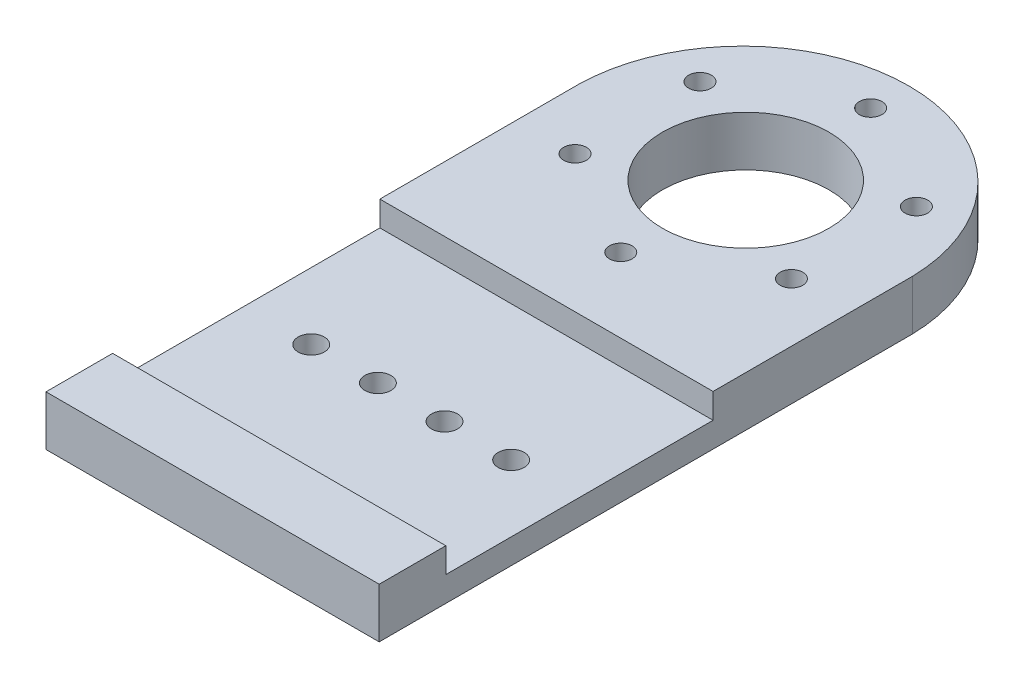
SolidWorks part; units mm, degrees
ref_plane "Front Plane" through (0, 0, 0) normal (0, 0, 1) x (1, 0, 0)
ref_plane "Top Plane" through (0, 0, 0) normal (0, 1, 0) x (1, 0, 0)
ref_plane "Right Plane" through (0, 0, 0) normal (1, 0, 0) x (0, 0, -1)
sketch "Sketch1" plane through (0, 0, 0) normal (0, 1, 0) x (1, 0, 0)
  line L0 (0, -111.3091) -> (63.5, -111.3091)
  line L2 (0, -22.4091) -> (0, -124.0091)
  line L3 (0, -124.0091) -> (63.5, -124.0091)
  line L4 (63.5, -22.4091) -> (63.5, -124.0091)
  line L5 (0, -9.7091) -> (50000, -9.7091) construction
  line L6 (31.75, -22.4091) -> (-49968.25, -22.4091) construction
  line L7 (0, -60.3821) -> (63.5, -60.3821)
  circle A0 centre (31.75, -22.4091) radius 15.875
  circle A1 centre (12.7, -86.1631) radius 2.4892
  circle A2 centre (25.4, -86.1631) radius 2.4892
  circle A3 centre (38.1, -86.1631) radius 2.4892
  circle A4 centre (50.8, -86.1631) radius 2.4892
  arc A8 (63.5, -22.4091) -> (0, -22.4091) centre (31.75, -23.0483) ccw
  point P25 (63.5, -9.7091)
  dimension "D3" = 31.75
  dimension "D5" = 31.75
  dimension "D6" = 4.9784
  dimension "D7" = 12.7
  dimension "D8" = 37.846
  dimension "D10" = 12.7
  dimension "D12" = 63.627
  dimension "D9" = 4
extrude "Boss-Extrude2" add sketch "Sketch1" along normal blind 9.525 contours L4 L0 L2 L3 | L2 L7 L4 A0 | L5 A0 region at (31.75, 0, 117.6591) region at (0.9384, 0, 41.3956)
extrude "Boss-Extrude3" add sketch "Sketch1<3>" along normal blind 4.7625 contours L7 L2 L0 L4 A4 A3 A2 A1 region at (31.75, 0, 85.8377)
sketch "Sketch1<3>" plane through (0, 0, 0) normal (0, 1, 0) x (1, 0, 0) same geometry as "Sketch1"
sketch "Sketch2" plane through (0, 0, 0) normal (0, -1, 0) x (1, 0, 0)
  line L0 (31.75, 22.4091) -> (11.1278, 34.3153) construction
  line L1 (31.75, 22.4091) -> (31.75, 46.2216) construction
  circle A0 centre (11.1278, 34.3153) radius 2.159
  circle A4 centre (31.75, 22.4091) radius 23.8125 construction
  circle A5 centre (31.75, 46.2216) radius 2.159
  circle A6 centre (52.3722, 34.3153) radius 2.159
  circle A7 centre (52.3722, 10.5028) radius 2.159
  circle A8 centre (31.75, -1.4034) radius 2.159
  circle A9 centre (11.1278, 10.5028) radius 2.159
  dimension "D1" = 4.318
  dimension "D3" = 60
  dimension "D4" = 47.625
  dimension "D2" = 6
extrude "Cut-Extrude1" cut sketch "Sketch2" against normal through all
